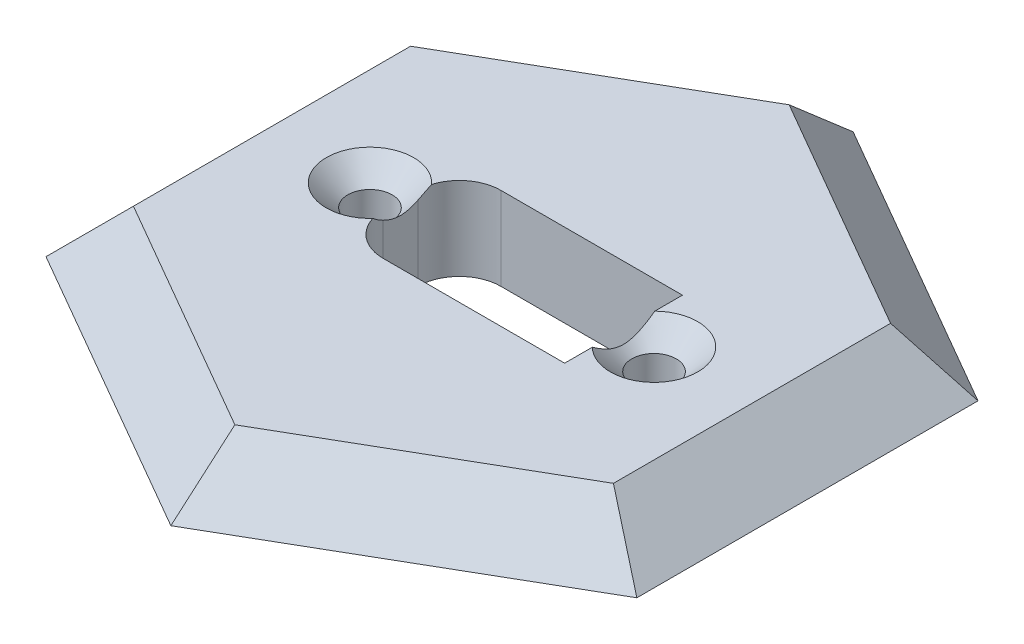
SolidWorks part; units mm, degrees
ref_plane "Płaszczyzna przednia" through (0, 0, 0) normal (0, 0, 1) x (1, 0, 0)
ref_plane "Płaszczyzna górna" through (0, 0, 0) normal (0, 1, 0) x (1, 0, 0)
ref_plane "Płaszczyzna prawa" through (0, 0, 0) normal (1, 0, 0) x (0, 0, -1)
sketch "Sketch1" plane through (0, 0, 0) normal (0, 1, 0) x (1, 0, 0)
  circle A0 centre (0, 0) radius 26
extrude "Boss-Extrude1" add sketch "Sketch1" along normal blind 4
sketch "Sketch3" plane through (0, 0, 0) normal (0, -1, 0) x (1, 0, 0)
  circle A0 centre (0, 0) radius 17
extrude "Boss-Extrude2" add sketch "Sketch3" along normal blind 2
sketch "Sketch2" plane through (0, 4, 0) normal (0, 1, 0) x (1, 0, 0)
  line L1 (-5.05, -4.25) -> (8.05, -4.25)
  line L2 (-8.05, -1.25) -> (-8.05, 1.25)
  line L3 (-5.05, 4.25) -> (8.05, 4.25)
  line L4 (8.05, -4.25) -> (8.05, 4.25)
  line L5 (-8.05, -4.25) -> (8.05, 4.25) construction
  line L6 (-8.05, 4.25) -> (8.05, -4.25) construction
  arc A0 (-5.05, -4.25) -> (-8.05, -1.25) centre (-5.05, -1.25) cw
  arc A1 (-8.05, 1.25) -> (-5.05, 4.25) centre (-5.05, 1.25) cw
  point P0 (0, 0)
  dimension "D3" = 3
  dimension "D1" = 8.5
  dimension "D2" = 16.1
extrude "Cut-Extrude1" cut sketch "Sketch2" against normal blind 20
sketch "Sketch4" plane through (0, 4, 0) normal (0, 1, 0) x (1, 0, 0)
  line L0 (0, 0) -> (-10.25, 0) construction
  line L1 (0, 0) -> (10.25, 0) construction
  circle A0 centre (-10.25, 0) radius 1.6
  circle A1 centre (10.25, 0) radius 1.6
extrude "Cut-Extrude2" cut sketch "Sketch4" against normal blind 10
sketch "Sketch6" plane through (0, 4, 0) normal (0, 1, 0) x (1, 0, 0)
  line L1 (0, 20) -> (-17.3205, 10)
  line L2 (-17.3205, 10) -> (-17.3205, -10)
  line L3 (-17.3205, -10) -> (0, -20)
  line L4 (0, -20) -> (17.3205, -10)
  line L5 (17.3205, -10) -> (17.3205, 10)
  line L6 (17.3205, 10) -> (0, 20)
  circle A0 centre (0, 0) radius 20 construction
  circle A1 centre (0, 0) radius 17.3205 construction
extrude "Cut-Extrude3" cut sketch "Sketch6" against normal blind 10 draft 45 flip side to cut
sketch "Sketch7" plane through (0, 4, 0) normal (0, 1, 0) x (1, 0, 0)
  line L0 (-8.05, 1.25) -> (-8.05, 2.0396)
  line L1 (-8.05, 2.0396) -> (-8.05, -2.0396)
  line L2 (8.05, 2.0396) -> (8.05, -2.0396)
  line L3 (8.05, -4.25) -> (8.05, 4.25) construction
  arc A0 (-8.05, 2.0396) -> (-8.05, -2.0396) centre (-10.25, 0) ccw
  arc A1 (8.05, -2.0396) -> (8.05, 2.0396) centre (10.25, 0) ccw
  circle A4 centre (-10.25, 0) radius 1.6
  circle A5 centre (10.25, 0) radius 1.6
sketch "Sketch9" plane through (0, 4, 0) normal (0, 1, 0) x (1, 0, 0)
  point P0 (-10.25, 0)
  point P3 (10.25, 0)
hole_wizard "CSK for M3 Countersunk Flat Head Screw2" positions "Sketch9" profile "Sketch10" countersink size "M3" standard "ISO" end condition through all
sketch "Sketch10" plane through (-10.25, 4, 0) normal (1, 0, 0) x (0, 0, 1)
  line L0 (0, 0) -> (0, 6)
  line L1 (0, 6) -> (1.6, 6)
  line L2 (1.6, 6) -> (1.6, 1.55)
  line L3 (1.6, 1.55) -> (3.15, 0)
  line L5 (3.15, 0) -> (0, 0)
  line L6 (-1.6, 1.55) -> (-3.15, 0) construction
  line L11 (0, -6.35) -> (0, 107.95) construction
  dimension "Thru Hole Dia." = 3.2
  dimension "Thru Hole Depth" = 6
  dimension "Near C'Sink Dia." = 6.3
  dimension "Near C'Sink Angle" = 90
